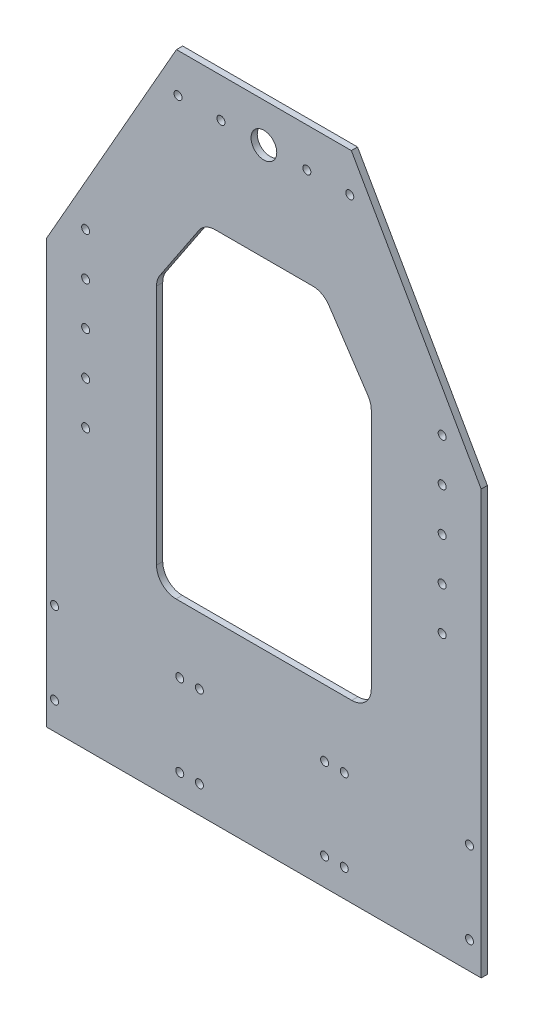
SolidWorks part; units mm, degrees
ref_plane "Front Plane" through (0, 0, 0) normal (0, 0, 1) x (1, 0, 0)
ref_plane "Top Plane" through (0, 0, 0) normal (0, 1, 0) x (1, 0, 0)
ref_plane "Right Plane" through (0, 0, 0) normal (1, 0, 0) x (0, 0, -1)
sketch "Sketch1" plane through (0, 0, 0) normal (0, 0, 1) x (1, 0, 0)
  line L0 (111.3, -111.5408) -> (111.3, 222.2553)
  line L1 (111.3, -111.5408) -> (-111.3, -111.5408)
  line L2 (111.3, 222.2553) -> (-111.3, 222.2553)
  line L3 (-111.3, -111.5408) -> (-111.3, 222.2553)
  line L4 (111.3, -111.5408) -> (-111.3, 222.2553) construction
  line L5 (111.3, 222.2553) -> (-111.3, -111.5408) construction
  line L6 (-95.7, -103.393) -> (-95.7, -89.9338) construction
  line L7 (-95.7, -51.0408) -> (-92.7, -51.0408)
  line L8 (-95.7, -51.0408) -> (-95.7, -92.0408)
  line L9 (-95.7, -92.0408) -> (-92.7, -92.0408)
  line L10 (-92.7, -51.0408) -> (-92.7, -92.0408)
  line L11 (-92.7, -104.2814) -> (-92.7, -92.5342) construction
  line L12 (-95.7, -51.5408) -> (-92.7, -51.5408) construction
  line L13 (-55.7, -107.2088) -> (-55.7, -104.2814) construction
  line L14 (-55.7, -51.0408) -> (-52.7, -51.0408)
  line L15 (-55.7, -51.0408) -> (-55.7, -92.0408)
  line L16 (-55.7, -92.0408) -> (-52.7, -92.0408)
  line L17 (-52.7, -51.0408) -> (-52.7, -92.0408)
  line L18 (-52.7, -103.393) -> (-52.7, -89.9338) construction
  line L20 (-52.7, -51.5408) -> (-55.7, -51.5408) construction
  line L22 (18.5, -51.0408) -> (18.5, -92.0408)
  line L23 (18.5, -51.0408) -> (21.5, -51.0408)
  line L24 (21.5, -51.0408) -> (21.5, -92.0408)
  line L25 (18.5, -92.0408) -> (21.5, -92.0408)
  line L26 (-21.5, -51.0408) -> (-21.5, -92.0408)
  line L27 (-21.5, -51.0408) -> (-18.5, -51.0408)
  line L28 (-18.5, -51.0408) -> (-18.5, -92.0408)
  line L29 (-21.5, -92.0408) -> (-18.5, -92.0408)
  line L30 (92.7, -51.0408) -> (92.7, -92.0408)
  line L31 (92.7, -51.0408) -> (95.7, -51.0408)
  line L32 (95.7, -51.0408) -> (95.7, -92.0408)
  line L33 (92.7, -92.0408) -> (95.7, -92.0408)
  line L34 (52.7, -51.0408) -> (52.7, -92.0408)
  line L35 (52.7, -51.0408) -> (55.7, -51.0408)
  line L36 (55.7, -51.0408) -> (55.7, -92.0408)
  line L37 (52.7, -92.0408) -> (55.7, -92.0408)
  point P1 (0, 0)
  dimension "D1" = 222.6
  dimension "D2" = 0.5
  dimension "D3" = 41
  dimension "D4" = 41
  dimension "D5" = 0.5
  dimension "D6" = 3
extrude "Boss-Extrude1" add sketch "Sketch1" along normal blind 6.35
sketch "Sketch2" plane through (0, 0, 0) normal (0, 0, -1) x (-1, 0, 0)
  line L0 (-111.3, -96.0005) -> (-37.1, -96.0005) construction
  line L1 (-111.3, -111.5408) -> (-111.3, 222.2553) construction
  line L2 (-73.2331, -96.0005) -> (-73.2331, -35.021) construction
  line L3 (0, 222.2553) -> (0, 172.1077) construction
  line L7 (-111.3, 222.2553) -> (111.3, 222.2553) construction
  line L9 (91.3, 20.2391) -> (91.3, 130.2391) construction
  line L10 (-44.7849, 222.2553) -> (-111.3, 105.3583)
  line L11 (-111.3, 105.3583) -> (-111.3, 222.2553)
  line L12 (-111.3, 222.2553) -> (-44.7849, 222.2553)
  line L13 (-44.7849, 222.2553) -> (44.7849, 222.2553) construction
  line L14 (-111.3, -111.5408) -> (-111.3, 105.3583) construction
  line L15 (111.3, 222.2553) -> (44.7849, 222.2553)
  line L16 (111.3, 105.3583) -> (111.3, 222.2553)
  line L17 (44.7849, 222.2553) -> (111.3, 105.3583)
  circle A0 centre (-105.3, -97.5408) radius 2.05
  circle A1 centre (-105.3, -55.5408) radius 2.05
  arc A2 (-103.45, -55.5408) -> (-103.6551, -56.3874) centre (-105.3, -55.5408) ccw construction
  circle A3 centre (-41.1662, -97.5408) radius 2.05
  circle A4 centre (-41.1662, -55.5408) radius 2.05
  circle A5 centre (-31.1, -97.5408) radius 2.05
  circle A6 centre (-31.1, -55.5408) radius 2.05
  circle A7 centre (33.0338, -97.5408) radius 2.05
  circle A8 centre (33.0338, -55.5408) radius 2.05
  circle A9 centre (43.1, -97.5408) radius 2.05
  circle A10 centre (43.1, -55.5408) radius 2.05
  circle A11 centre (107.2338, -97.5408) radius 2.05
  circle A12 centre (107.2338, -55.5408) radius 2.05
  circle A13 centre (0, 202.2553) radius 6.5893
  circle A14 centre (-91.3, 31.2391) radius 2.05
  circle A15 centre (91.3, 31.2391) radius 2.05
  circle A16 centre (91.3, 53.2391) radius 2.05
  circle A17 centre (-91.3, 53.2391) radius 2.05
  circle A18 centre (91.3, 75.2391) radius 2.05
  circle A19 centre (-91.3, 75.2391) radius 2.05
  circle A20 centre (91.3, 97.2391) radius 2.05
  circle A21 centre (-91.3, 97.2391) radius 2.05
  circle A22 centre (91.3, 119.2391) radius 2.05
  circle A23 centre (-91.3, 119.2391) radius 2.05
  circle A24 centre (44, 202.2553) radius 2.05
  circle A25 centre (22, 202.2553) radius 2.05
  circle A26 centre (-22, 202.2553) radius 2.05
  circle A27 centre (-44, 202.2553) radius 2.05
  ellipse E0 centre (0, 202.2553) end of major axis (55, 202.2553) minor radius 20 construction
  ellipse E1 centre (-91.3, 75.2391) end of major axis (-91.3031, 20.2391) minor radius 20 construction
  spline S0 degree 3 poles (-91.4672, 20.2391) (-90.6311, 20.2391) (-89.9748, 20.3093) (-89.0076, 20.5123) (-88.6882, 20.5964) (-88.055, 20.7969) (-87.7407, 20.9138) (-86.825, 21.3043) (-86.2443, 21.619) (-85.412, 22.1617) (-85.1401, 22.3551) (-84.6127, 22.761) (-84.3581, 22.9726) (-83.1253, 24.0687) (-82.2659, 25.0655) (-81.1013, 26.6787) (-80.7377, 27.2321) (-80.0534, 28.3565) (-79.732, 28.9289) (-78.8181, 30.6707) (-78.2752, 31.8643) (-77.5313, 33.6892) (-77.2952, 34.3034) (-76.8439, 35.5418) (-76.6286, 36.1661) (-75.6041, 39.2906) (-74.9396, 41.8152) (-73.8084, 46.8963) (-73.3439, 49.4531) (-72.5684, 54.5917) (-72.258, 57.1734) (-71.7687, 62.3581) (-71.59, 64.9611) (-71.4131, 68.8803) (-71.3694, 70.1897) (-71.3123, 72.8036) (-71.2988, 74.1092) (-71.3027, 78.0222) (-71.3645, 80.6257) (-71.6091, 85.822) (-71.7918, 88.4148) (-72.2901, 93.5889) (-72.6055, 96.1702) (-73.3946, 101.3188) (-73.8676, 103.8862) (-74.7356, 107.7235) (-75.052, 109.0011) (-75.7445, 111.5305) (-76.121, 112.7844) (-76.9498, 115.2653) (-77.4019, 116.4924) (-78.1558, 118.306) (-78.4198, 118.9061) (-78.9783, 120.0953) (-79.2732, 120.6855) (-80.2105, 122.4293) (-80.8999, 123.5501) (-82.0815, 125.136) (-82.5017, 125.6497) (-83.3887, 126.6179) (-83.8567, 127.0745) (-84.8524, 127.9209) (-85.3799, 128.3109) (-86.2269, 128.8335) (-86.5169, 128.996) (-87.1058, 129.2925) (-87.4057, 129.4271) (-88.017, 129.6676) (-88.3284, 129.7735) (-88.9634, 129.9549) (-89.2889, 130.0307) (-90.2671, 130.2057) (-90.9213, 130.2542) (-91.9059, 130.2255) (-92.2346, 130.1989) (-92.8932, 130.1108) (-93.2205, 130.0495) (-94.1828, 129.8189) (-94.804, 129.6022) (-95.7078, 129.1902) (-96.0049, 129.0378) (-96.5793, 128.7113) (-96.858, 128.5367) (-97.671, 127.9816) (-98.1823, 127.5703) (-99.1533, 126.6783) (-99.6131, 126.1966) (-100.4694, 125.1994) (-100.8692, 124.6809) (-102.0015, 123.0782) (-102.6687, 121.9455) (-103.8788, 119.6036) (-104.4131, 118.4108) (-105.3857, 115.9955) (-105.8234, 114.7728) (-107.0274, 111.071) (-107.6865, 108.5588) (-108.8124, 103.4749) (-109.2782, 100.8965) (-110.0499, 95.7466) (-110.3569, 93.1692) (-110.8395, 88.0104) (-111.0149, 85.429) (-111.2463, 80.2626) (-111.3022, 77.6776) (-111.2977, 72.5039) (-111.2373, 69.9154) (-110.9957, 64.7345) (-110.8145, 62.1422) (-110.4416, 58.2507) (-110.3003, 56.9527) (-109.9819, 54.3644) (-109.8047, 53.073) (-109.4109, 50.4965) (-109.1942, 49.2113) (-108.7163, 46.648) (-108.4548, 45.3687) (-107.594, 41.5516) (-106.9224, 39.0371) (-105.693, 35.3336) (-105.2457, 34.1106) (-104.499, 32.2996) (-104.237, 31.699) (-103.6858, 30.5145) (-103.3965, 29.9299) (-102.4792, 28.2034) (-101.8027, 27.0867) (-100.2545, 24.9698) (-99.3984, 23.9902) (-98.1734, 22.9149) (-97.9205, 22.7074) (-97.3969, 22.3096) (-97.1273, 22.1202) (-96.3027, 21.5891) (-95.7286, 21.2818) (-94.5245, 20.7739) (-93.89, 20.5734) (-92.9306, 20.3741) (-92.6082, 20.3238) (-92.1206, 20.2732) (-91.9574, 20.2605) (-91.6297, 20.2434) (-91.4672, 20.2391) (-90.6311, 20.2391) (-89.9748, 20.3093) knots -0.001953 -0.001953 0 0 0.007812 0.007812 0.011719 0.011719 0.015625 0.015625 0.023437 0.023437 0.027344 0.027344 0.03125 0.03125 0.046875 0.046875 0.054687 0.054687 0.0625 0.0625 0.078125 0.078125 0.085937 0.085937 0.09375 0.09375 0.125 0.125 0.15625 0.15625 0.1875 0.1875 0.21875 0.21875 0.234375 0.234375 0.25 0.25 0.28125 0.28125 0.3125 0.3125 0.34375 0.34375 0.375 0.375 0.390625 0.390625 0.40625 0.40625 0.421875 0.421875 0.429688 0.429688 0.4375 0.4375 0.453125 0.453125 0.460938 0.460938 0.46875 0.46875 0.476563 0.476563 0.480469 0.480469 0.484375 0.484375 0.488281 0.488281 0.492188 0.492188 0.5 0.5 0.503906 0.503906 0.507813 0.507813 0.515625 0.515625 0.519531 0.519531 0.523438 0.523438 0.53125 0.53125 0.539063 0.539063 0.546875 0.546875 0.5625 0.5625 0.578125 0.578125 0.59375 0.59375 0.625 0.625 0.65625 0.65625 0.6875 0.6875 0.71875 0.71875 0.75 0.75 0.78125 0.78125 0.8125 0.8125 0.828125 0.828125 0.84375 0.84375 0.859375 0.859375 0.875 0.875 0.90625 0.90625 0.921875 0.921875 0.929687 0.929687 0.9375 0.9375 0.953125 0.953125 0.96875 0.96875 0.972656 0.972656 0.976562 0.976562 0.984375 0.984375 0.992187 0.992187 0.996094 0.996094 0.998047 0.998047 1 1 1.007812 1.007812 1.011719 only from (-91.3, 20.2391) to (-91.3, 20.2391) construction
  point P89 (0, 0)
  point P90 (-91.3, 10.8589)
  point P93 (-91.3, 20.2391)
  dimension "D1" = 4.1
  dimension "D4" = 4.1
  dimension "3/8in" = 13.1786
  dimension "D2" = 74.2
  dimension "D6" = 22
  dimension "D3" = 3
  dimension "D5" = 5
extrude "Cut-Extrude1" cut sketch "Sketch2" against normal blind 10
sketch "Sketch3" plane through (0, 0, 6.35) normal (0, 0, 1) x (1, 0, 0)
  line L0 (44.7849, 222.2553) -> (-44.7849, 222.2553) construction
  line L1 (-111.3, 222.2553) -> (111.3, 222.2553)
  line L2 (-111.3, 222.2553) -> (-111.3, -111.5408)
  line L3 (-111.3, -111.5408) -> (111.3, -111.5408)
  line L4 (111.3, 222.2553) -> (111.3, -111.5408)
  point P6 (0, 0)
extrude "Cut-Extrude2" cut sketch "Sketch3" against normal blind 3.175
sketch "Sketch4" plane through (0, 0, 3.175) normal (0, 0, 1) x (1, 0, 0)
  line L1 (-95.7, -51.0408) -> (-52.7, -51.0408)
  line L2 (-95.7, -51.0408) -> (-95.7, -92.0408)
  line L3 (-95.7, -92.0408) -> (-52.7, -92.0408)
  line L4 (-52.7, -51.0408) -> (-52.7, -92.0408)
  line L5 (-21.5, -51.0408) -> (21.5, -51.0408)
  line L6 (-21.5, -51.0408) -> (-21.5, -92.0408)
  line L7 (-21.5, -92.0408) -> (21.5, -92.0408)
  line L8 (21.5, -51.0408) -> (21.5, -92.0408)
  line L9 (52.7, -51.0408) -> (95.7, -51.0408)
  line L10 (52.7, -51.0408) -> (52.7, -92.0408)
  line L11 (52.7, -92.0408) -> (95.7, -92.0408)
  line L12 (95.7, -51.0408) -> (95.7, -92.0408)
extrude "Boss-Extrude2" add sketch "Sketch4" against normal up to surface (3.175 mm away) up to face at (89.25, 53.2391, 0)
sketch "Sketch6" plane through (0, 0, 0) normal (0, 0, -1) x (-1, 0, 0)
  line L0 (0, -111.5408) -> (0, 222.2553) construction
  line L1 (111.3, -111.5408) -> (-111.3, -111.5408) construction
  line L2 (-44.7849, 222.2553) -> (44.7849, 222.2553) construction
  line L3 (0, 152.2553) -> (-25, 152.2553)
  line L4 (-33.3205, 147.8023) -> (-53.3205, 117.8023)
  line L5 (-55, 112.2553) -> (-55, -11.5408)
  line L6 (-45, -21.5408) -> (45, -21.5408)
  line L7 (55, 112.2553) -> (55, -11.5408)
  line L8 (33.3205, 147.8023) -> (53.3205, 117.8023)
  line L9 (0, 152.2553) -> (25, 152.2553)
  arc A0 (-55, -11.5408) -> (-45, -21.5408) centre (-45, -11.5408) ccw
  arc A1 (-53.3205, 117.8023) -> (-55, 112.2553) centre (-45, 112.2553) ccw
  arc A2 (-25, 152.2553) -> (-33.3205, 147.8023) centre (-25, 142.2553) ccw
  arc A3 (25, 152.2553) -> (33.3205, 147.8023) centre (25, 142.2553) cw
  arc A4 (53.3205, 117.8023) -> (55, 112.2553) centre (45, 112.2553) cw
  arc A5 (55, -11.5408) -> (45, -21.5408) centre (45, -11.5408) cw
  point P17 (-12.5, 152.2553)
  point P18 (-25, 147.9134)
  point P28 (0, -21.5408)
  dimension "D1" = 10
  dimension "D2" = 55
  dimension "D3" = 90
  dimension "D4" = 40
  dimension "D5" = 25
  dimension "D6" = 70
extrude "Cut-Extrude3" cut sketch "Sketch6" against normal blind 3.175
equation "\"D4@Sketch1\"=\"D3@Sketch1\""
